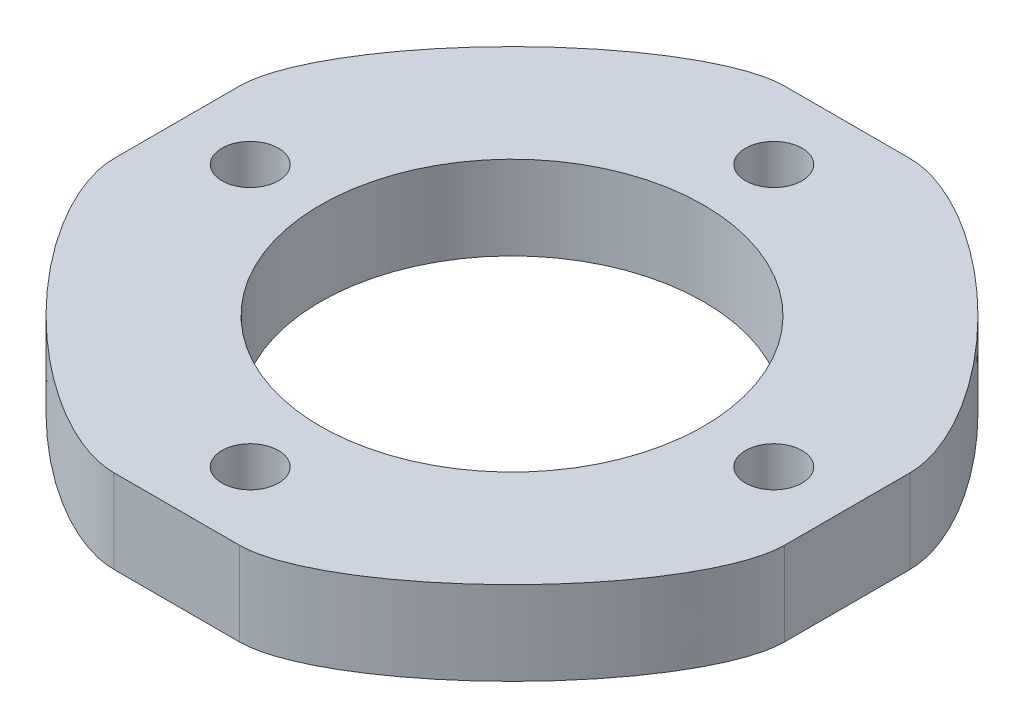
SolidWorks part; units mm, degrees
ref_plane "Front" through (0, 0, 0) normal (0, 0, 1) x (1, 0, 0)
ref_plane "Top" through (0, 0, 0) normal (0, 1, 0) x (1, 0, 0)
ref_plane "Right" through (0, 0, 0) normal (1, 0, 0) x (0, 0, -1)
sketch "Sketch1" plane through (0, 0, 0) normal (0, 1, 0) x (1, 0, 0)
  line L1 (0, 0) -> (32, 0)
  line L2 (0, 0) -> (0, -32)
  line L3 (0, -32) -> (32, -32)
  line L4 (32, 0) -> (32, -32)
  dimension "D1" = 32
  dimension "D2" = 32
extrude "Boss-Extrude1" add sketch "Sketch1" along normal blind 4
sketch "Sketch2" plane through (0, 0, 0) normal (0, -1, 0) x (-1, 0, 0)
  line L0 (-32, 0) -> (0, 0) construction
  line L1 (-32, -32) -> (-32, 0) construction
  line L2 (0, -32) -> (-32, -32) construction
  line L3 (0, 0) -> (0, -32) construction
  circle A0 centre (-16, -16) radius 9.15
  circle A1 centre (-16, -28.5) radius 1.35
  circle A2 centre (-28.5, -16) radius 1.35
  circle A3 centre (-16, -3.5) radius 1.35
  circle A4 centre (-3.5, -16) radius 1.35
  dimension "D1" = 18.3
  dimension "D2" = 2.7
  dimension "D3" = 2.7
  dimension "D4" = 2.7
  dimension "D5" = 2.7
  dimension "D6" = 3.5
  dimension "D7" = 3.5
  dimension "D8" = 3.5
  dimension "D9" = 3.5
extrude "Cut-Extrude1" cut sketch "Sketch2" against normal blind 4
fillet "Fillet1" radius 13 4 edges at (0, 2, 0) (32, 2, 0) (32, 2, 32) (0, 2, 32) conic rho 0.25
